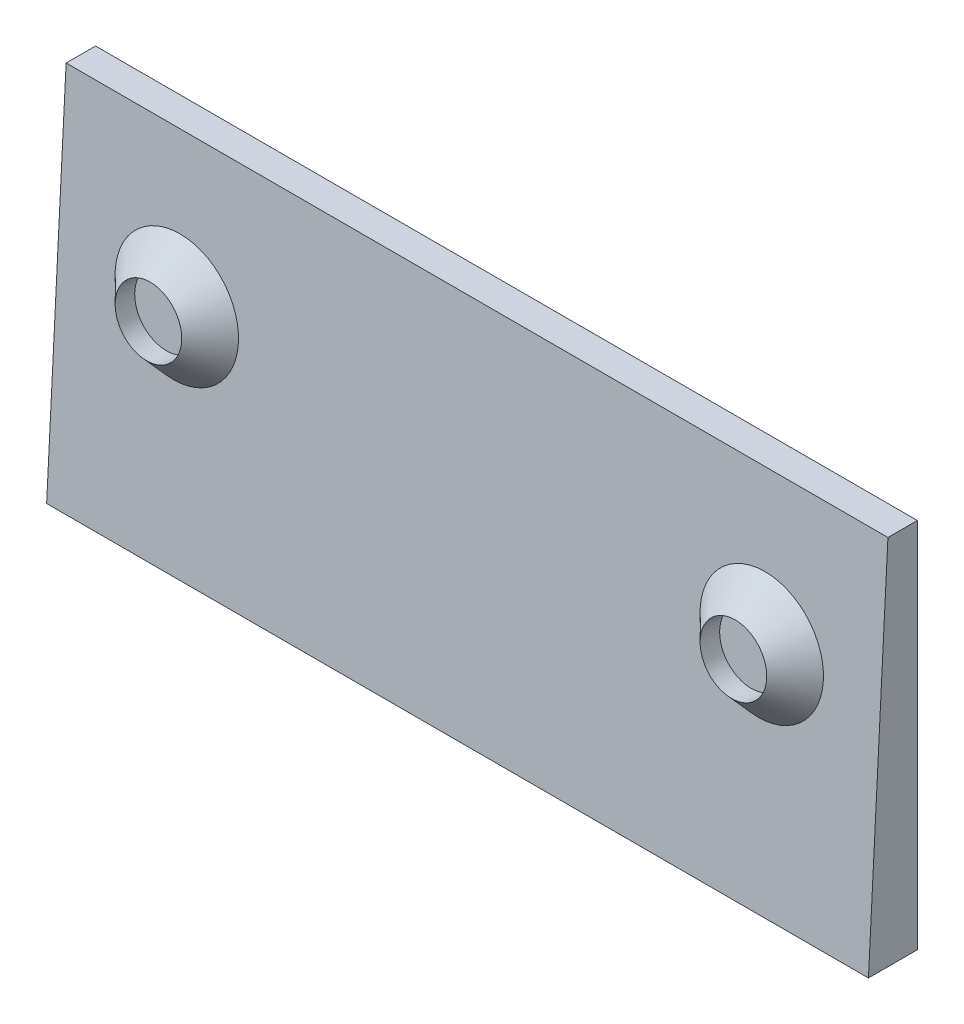
SolidWorks part; units mm, degrees
ref_plane "Top Plane" through (0, 0, 0) normal (0, 0, 1) x (1, 0, 0)
ref_plane "Front Plane" through (0, 0, 0) normal (0, 1, 0) x (1, 0, 0)
ref_plane "Right Plane" through (0, 0, 0) normal (1, 0, 0) x (0, 0, -1)
sketch "Sketch1" plane through (0, 0, 0) normal (0, 0, 1) x (1, 0, 0)
  line L1 (-42, -19) -> (42, -19)
  line L2 (-42, -19) -> (-42, 19)
  line L3 (-42, 19) -> (42, 19)
  line L4 (42, -19) -> (42, 19)
  line L5 (-42, -19) -> (42, 19) construction
  line L6 (-42, 19) -> (42, -19) construction
  point P0 (0, 0)
  dimension "D1" = 84
  dimension "D2" = 38
extrude "Boss-Extrude1" add sketch "Sketch1" along normal blind 5
sketch "Sketch2" plane through (0, 0, 5) normal (0, 0, 1) x (1, 0, 0)
  line L1 (-42, -19) -> (42, -19)
  line L2 (-42, -19) -> (-42, 22.1553)
  line L3 (-42, 22.1553) -> (42, 22.1553)
  line L4 (42, -19) -> (42, 22.1553)
revolve "Cut-Revolve1" cut sketch "Sketch2" angle 3 about L1 reverse direction yes
sketch "Sketch3" plane through (0, 0.2093, 3.9933) normal (0, 0.0523, 0.9986) x (1, 0, 0)
  circle A0 centre (-29.8957, 3.6644) radius 6.3
  circle A1 centre (29.8957, 3.6644) radius 6.3
ref_plane "Plane1" through (0, 0.2564, 4.8921) normal (0, -0.0523, -0.9986) x (-1, 0, 0)
ref_plane "Plane2" through (0, 0.3611, 6.8893) normal (0, -0.0523, -0.9986) x (-1, 0, 0)
sketch "Sketch5" plane through (0, 0.3611, 6.8893) normal (0, -0.0523, -0.9986) x (-1, 0, 0)
  circle A0 centre (-29.8957, 3.6644) radius 3.4
  circle A1 centre (29.8957, 3.6644) radius 3.4
loft "Loft2" add section "Sketch5" section "Sketch3" connector at (-27.2805, 6.1902, 6.5838) connector at (-24.8648, 7.6556, 3.603)
loft "Loft3" add section "Sketch3<4>" section "Sketch5<4>" connector at (23.5963, 3.7817, 3.8061) connector at (26.4959, 3.9777, 6.6998)
sketch "Sketch3<4>" plane through (0, 0.2093, 3.9933) normal (0, 0.0523, 0.9986) x (1, 0, 0) same geometry as "Sketch3"
sketch "Sketch5<4>" plane through (0, 0.3611, 6.8893) normal (0, -0.0523, -0.9986) x (-1, 0, 0) same geometry as "Sketch5"
extrude "Cut-Extrude1" cut sketch "Sketch5<5>" along normal blind 2
sketch "Sketch5<5>" plane through (0, 0.3611, 6.8893) normal (0, -0.0523, -0.9986) x (-1, 0, 0) same geometry as "Sketch5"
